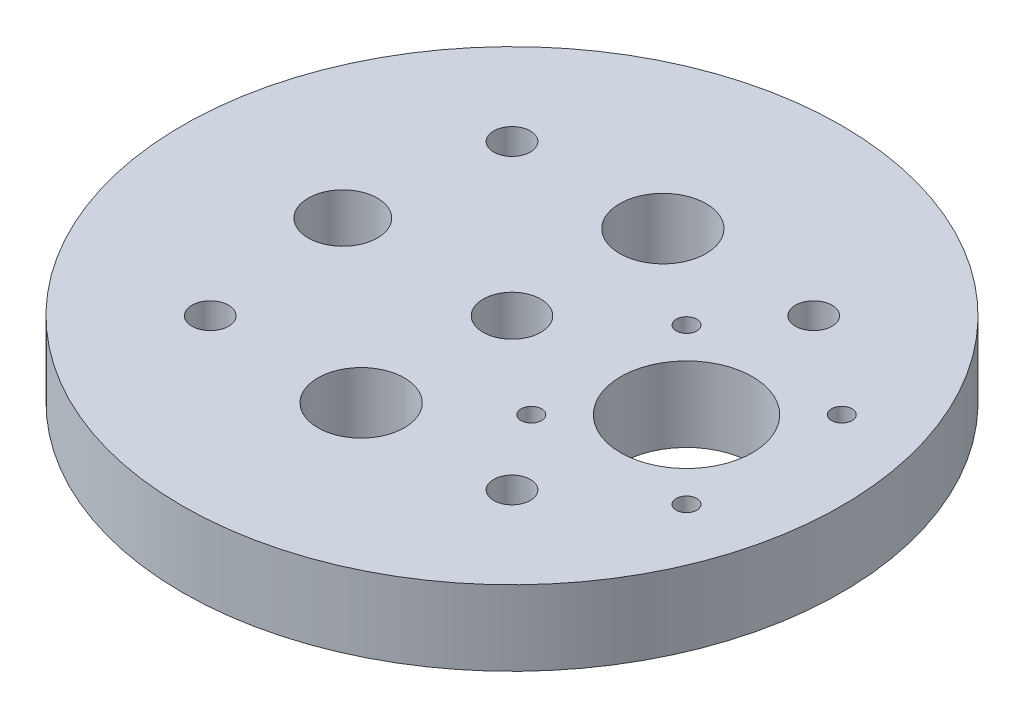
SolidWorks part; units mm, degrees
ref_plane "Front Plane" through (0, 0, 0) normal (0, 0, 1) x (1, 0, 0)
ref_plane "Top Plane" through (0, 0, 0) normal (0, 1, 0) x (1, 0, 0)
ref_plane "Right Plane" through (0, 0, 0) normal (1, 0, 0) x (0, 0, -1)
sketch "Sketch2" plane through (0, 0, 0) normal (0, 1, 0) x (1, 0, 0)
  circle A0 centre (0, 0) radius 57.15
  dimension "D1" = 114.3
extrude "Boss-Extrude1" add sketch "Sketch2" along normal blind 13 contours A0
sketch "Sketch6" plane through (0, 13, 0) normal (0, 1, 0) x (1, 0, 0)
  circle A0 centre (-26.1629, -26.1629) radius 3.175
  circle A1 centre (26.1629, -26.1629) radius 3.175
  circle A2 centre (-26.1629, 26.1631) radius 3.175
  circle A3 centre (26.1629, 26.1631) radius 3.175
  dimension "D1" = 6.35
  dimension "D2" = 74
  dimension "D3" = 26.1629
  dimension "D4" = 26.1629
  dimension "D5" = 26.1629
extrude "Cut-Extrude1" cut sketch "Sketch6" against normal up to next
sketch "Sketch7" plane through (0, 13, 0) normal (0, 1, 0) x (1, 0, 0)
  circle A0 centre (30, 0.2699) radius 11.43
  circle A3 centre (16.54, -13.1941) radius 1.778
  circle A4 centre (16.54, 13.7299) radius 1.778
  circle A5 centre (43.46, 13.7299) radius 1.778
  circle A6 centre (43.46, -13.1941) radius 1.778
  dimension "D1" = 22.86
  dimension "D2" = 3.556
  dimension "D3" = 3.556
  dimension "D4" = 3.556
  dimension "D5" = 3.556
  dimension "D6" = 13.46
  dimension "D7" = 13.46
  dimension "D8" = 13.46
  dimension "D9" = 13.464
  dimension "D10" = 30
extrude "Cut-Extrude2" cut sketch "Sketch7" against normal through all
sketch "Sketch8" plane through (0, 13, 0) normal (0, 1, 0) x (1, 0, 0)
  circle A0 centre (0, -26.1629) radius 7.5
  circle A1 centre (0, 26.1631) radius 7.5
  circle A2 centre (0, 0) radius 5
  circle A3 centre (-29.3379, 0) radius 6
  dimension "D1" = 15
  dimension "D2" = 15
  dimension "D3" = 10
  dimension "D4" = 12
extrude "Cut-Extrude3" cut sketch "Sketch8" against normal through all
equation "\"width\"=26.1629"
equation "\"D4@Sketch6\"=\"width\""
equation "\"D3@Sketch6\"=\"width\""
equation "\"D5@Sketch6\"=\"width\""
